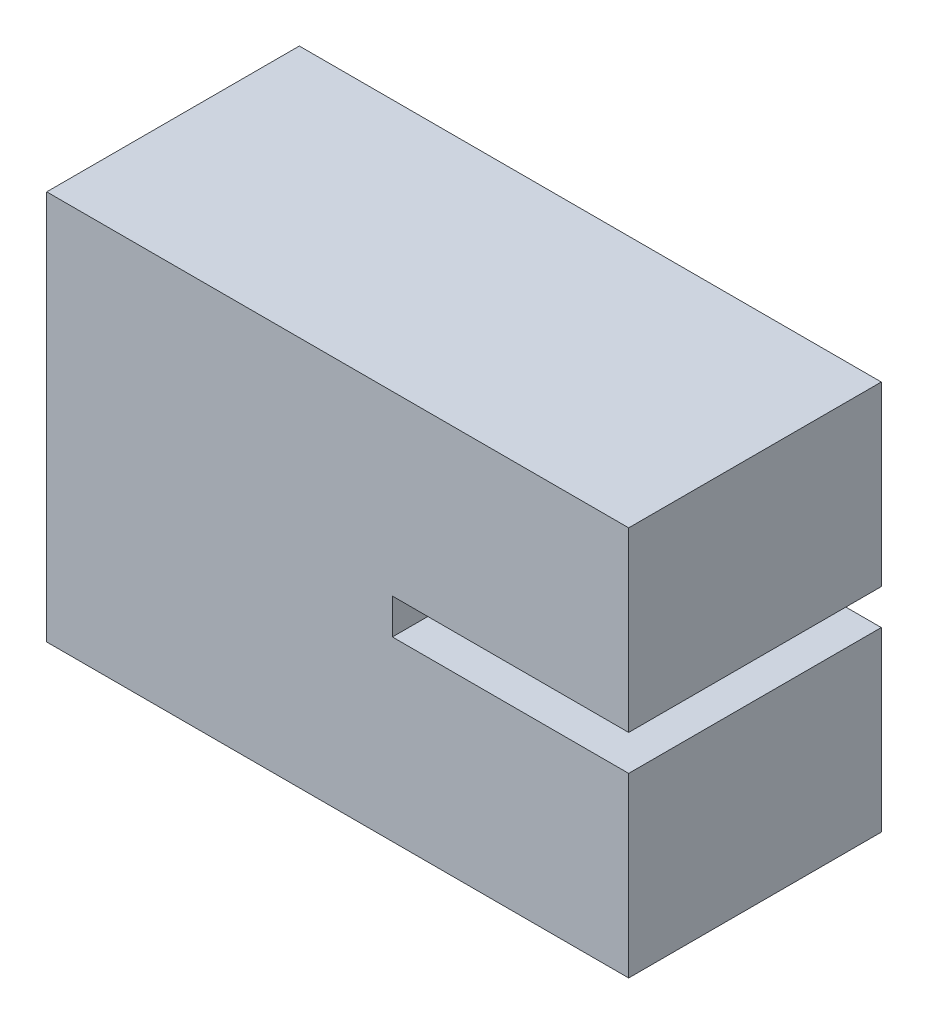
SolidWorks part; units mm, degrees
ref_plane "Front Plane" through (0, 0, 0) normal (0, 0, 1) x (1, 0, 0)
ref_plane "Top Plane" through (0, 0, 0) normal (0, 1, 0) x (1, 0, 0)
ref_plane "Right Plane" through (0, 0, 0) normal (1, 0, 0) x (0, 0, -1)
sketch "Sketch1" plane through (0, 0, 0) normal (0, 0, 1) x (1, 0, 0)
  line L0 (0, 0) -> (0, 13.2)
  line L1 (0, 13.2) -> (19.7046, 13.2)
  line L2 (19.7046, 13.2) -> (19.7046, 7.2)
  line L3 (19.7046, 7.2) -> (11.7046, 7.2)
  line L4 (11.7046, 7.2) -> (11.7046, 6)
  line L5 (11.7046, 6) -> (19.7046, 6)
  line L6 (19.7046, 6) -> (19.7046, 0)
  line L7 (19.7046, 0) -> (0, 0)
  point P4 (0, 0)
  point P10 (0, 0)
  dimension "D1" = 8
  dimension "D2" = 1.2
  dimension "D3" = 6
extrude "Boss-Extrude1" add sketch "Sketch1" along normal blind 8.553
